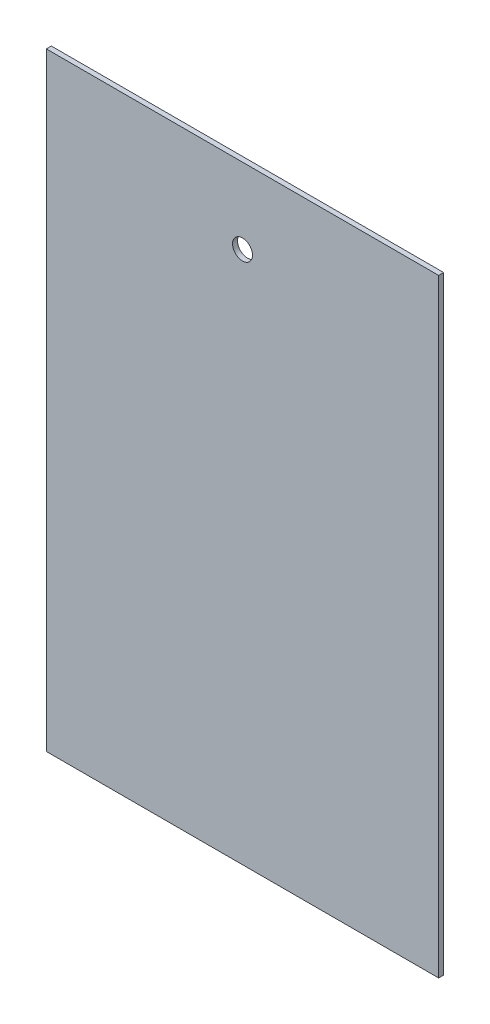
SolidWorks part; units mm, degrees
ref_plane "Alzado" through (0, 0, 0) normal (0, 0, 1) x (1, 0, 0)
ref_plane "Planta" through (0, 0, 0) normal (0, 1, 0) x (1, 0, 0)
ref_plane "Vista lateral" through (0, 0, 0) normal (1, 0, 0) x (0, 0, -1)
sketch "Sketch1" plane through (0, 0, 0) normal (0, 0, 1) x (1, 0, 0)
  line L1 (-118, 183) -> (118, 183)
  line L2 (-118, 183) -> (-118, -183)
  line L3 (-118, -183) -> (118, -183)
  line L4 (118, 183) -> (118, -183)
  line L5 (-118, 183) -> (118, -183) construction
  line L6 (-118, -183) -> (118, 183) construction
  point P0 (0, 0)
  dimension "D1" = 236
  dimension "D2" = 366
extrude "Boss-Extrude1" add sketch "Sketch1" along normal blind 3
sketch "Sketch2" plane through (0, 0, 0) normal (0, 0, -1) x (-1, 0, 0)
  circle A1 centre (0, 137.5) radius 6
  dimension "D1" = 12
extrude "Cut-Extrude2" cut sketch "Sketch2" against normal up to next
sketch "Sketch3" [suppressed] plane through (0, 0, 3) normal (0, 0, 1) x (1, 0, 0)
  circle A0 centre (0, 0) radius 10
  circle A1 centre (-58.75, -62.75) radius 9
  circle A2 centre (58.75, -62.75) radius 9
  circle A3 centre (0, 137.0156) radius 9
  dimension "D1" = 18
  dimension "D2" = 20
extrude "Cut-Extrude3" [suppressed] cut sketch "Sketch3" against normal up to next
